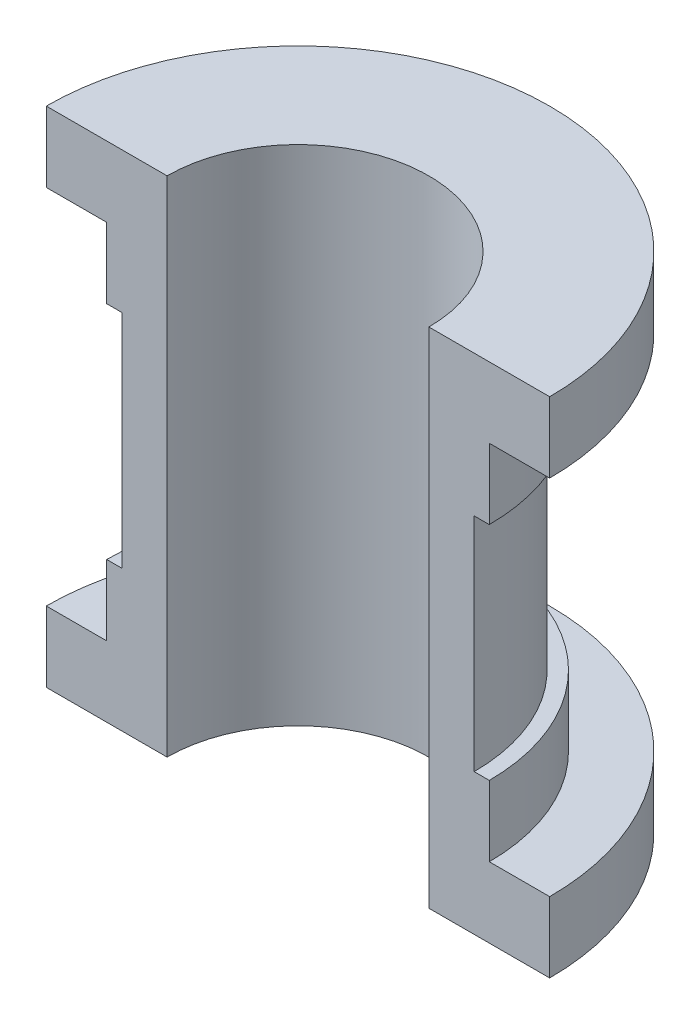
SolidWorks part; units mm, degrees
ref_plane "Front Plane" through (0, 0, 0) normal (0, 0, 1) x (1, 0, 0)
ref_plane "Top Plane" through (0, 0, 0) normal (0, 1, 0) x (1, 0, 0)
ref_plane "Right Plane" through (0, 0, 0) normal (1, 0, 0) x (0, 0, -1)
sketch "Sketch2" plane through (0, 0, 0) normal (0, 1, 0) x (1, 0, 0)
  line L0 (-25, 0) -> (25, 0)
  arc A0 (13, 0) -> (-13, 0) centre (0, 0) ccw
  arc A1 (25, 0) -> (-25, 0) centre (0, 0) ccw
extrude "Boss-Extrude2" add sketch "Sketch2" against normal blind 7 contours L0 A1 A0 region at (0, 0, -24.441)
ref_plane "Plane1" through (0, -7, 0) normal (0, 1, 0) x (1, 0, 0)
sketch "Sketch5" plane through (0, -7, 0) normal (0, 1, 0) x (1, 0, 0)
  line L0 (-19, 0) -> (19, 0)
  arc A0 (17.5, 0) -> (-17.5, 0) centre (0, 0) ccw
  arc A1 (19, 0) -> (-19, 0) centre (0, 0) ccw
extrude "Boss-Extrude3" add sketch "Sketch5" against normal blind 7 contours L0 A1 A0 region at (0, -7, -18.5751)
sketch "Sketch6" plane through (0, -7, 0) normal (0, 1, 0) x (1, 0, 0)
  line L0 (-17.5, 0) -> (17.5, 0)
  arc A0 (17.5, 0) -> (-17.5, 0) centre (0, 0) ccw
extrude "Boss-Extrude4" add sketch "Sketch6" against normal blind 18
sketch "Sketch7" plane through (0, -7, 0) normal (0, 1, 0) x (1, 0, 0)
  line L0 (-13, 0) -> (13, 0) construction
  circle A0 centre (0, 0) radius 13
extrude "Cut-Extrude3" cut sketch "Sketch7" against normal blind 18
ref_plane "Plane2" through (0, -14, 0) normal (0, 1, 0) x (1, 0, 0)
sketch "Sketch10" plane through (0, -14, 0) normal (0, 1, 0) x (1, 0, 0)
  line L0 (-19, 0) -> (-17.5, 0)
  line L1 (17.5, 0) -> (19, 0)
  line L2 (-19, 0) -> (-17.5, 0)
  line L3 (17.5, 0) -> (19, 0)
ref_plane "Plane4" through (0, -50, 0) normal (0, -1, 0) x (-1, 0, 0)
sketch "Sketch15" plane through (0, -50, 0) normal (0, -1, 0) x (-1, 0, 0)
  line L0 (-25, 0) -> (25, 0)
  arc A0 (25, 0) -> (-25, 0) centre (0, 0) ccw
  arc A1 (13, 0) -> (-13, 0) centre (0, 0) ccw
extrude "Boss-Extrude7" add sketch "Sketch15" against normal blind 7 separate body contours A1 L0 A0 region at (0, -50, -24.441)
sketch "Sketch16" plane through (0, -43, 0) normal (0, 1, 0) x (1, 0, 0)
  line L0 (-19, 0) -> (19, 0)
  arc A0 (17.5, 0) -> (-17.5, 0) centre (0, 0) ccw
  arc A1 (19, 0) -> (-19, 0) centre (0, 0) ccw
  arc M4 (-13, 0) -> (13, 0) centre (0, 0) cw
  line M5 (13, 0) -> (25, 0)
extrude "Boss-Extrude9" add sketch "Sketch16" along normal blind 18 contours A0 L0 M5 M4 region at (0, -43, -17.1087)
sketch "Sketch18" plane through (0, -43, 0) normal (0, 1, 0) x (1, 0, 0)
  line L0 (-19, 0) -> (19, 0)
  arc A0 (17.5, 0) -> (-17.5, 0) centre (0, 0) ccw
  arc A1 (19, 0) -> (-19, 0) centre (0, 0) ccw
  arc M2 (-17.5, 0) -> (17.5, 0) centre (0, 0) cw
  line M3 (17.5, 0) -> (25, 0)
  line M5 (-25, 0) -> (-17.5, 0)
extrude "Boss-Extrude10" add sketch "Sketch18" along normal blind 7 contours A1 M3 M5 M2 region at (0, -43, -18.5751)
ref_plane "Plane5" through (0, 0, -17.5) normal (0, 0, 1) x (1, 0, 0)
sketch "Sketch19" plane through (0, 0, -17.5) normal (0, 0, 1) x (1, 0, 0)
  circle A0 centre (0, -25) radius 3
extrude "Boss-Extrude11" add sketch "Sketch19" against normal blind 5 separate body
